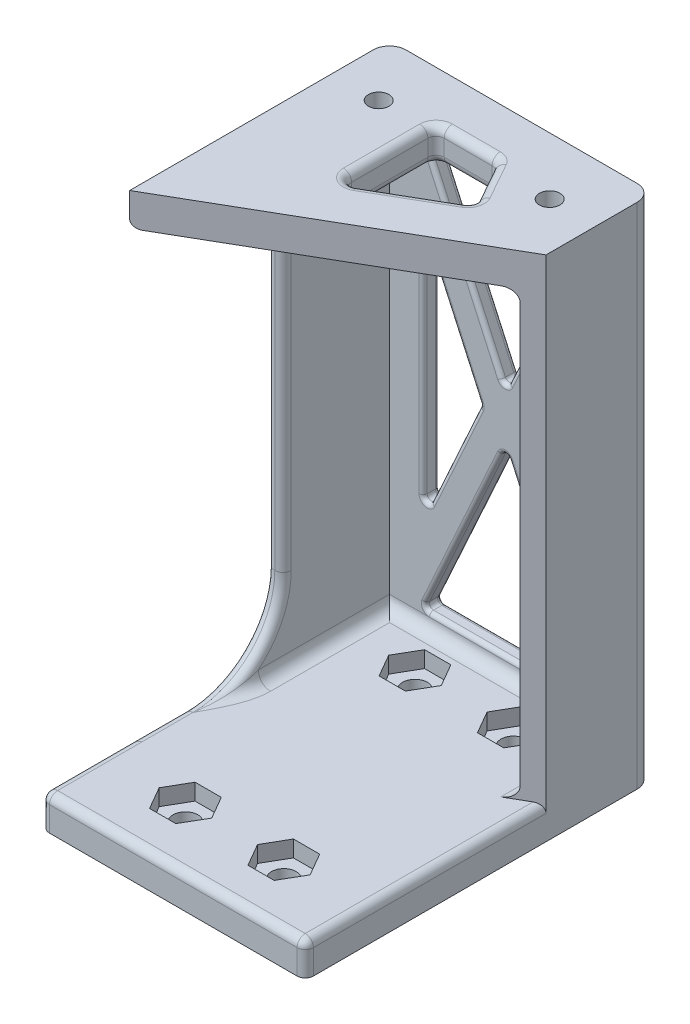
SolidWorks part; units mm, degrees
ref_plane "Front Plane" through (0, 0, 0) normal (0, 0, 1) x (1, 0, 0)
ref_plane "Top Plane" through (0, 0, 0) normal (0, 1, 0) x (1, 0, 0)
ref_plane "Right Plane" through (0, 0, 0) normal (1, 0, 0) x (0, 0, -1)
sketch "Sketch1" plane through (0, 0, 0) normal (0, 1, 0) x (1, 0, 0)
  line L1 (0, 0) -> (32.2, 0)
  line L2 (0, 0) -> (0, 34.25)
  line L3 (0, 34.25) -> (32.2, 34.25)
  line L4 (32.2, 0) -> (32.2, 34.25)
  dimension "D1" = 34.25
  dimension "D2" = 32.2
extrude "Boss-Extrude1" add sketch "Sketch1" along normal blind 4
sketch "Sketch2" plane through (0, 4, 0) normal (0, 1, 0) x (1, 0, 0)
  line L0 (32.2, 34.25) -> (0, 34.25) construction
  line L3 (16.1, 27.25) -> (10.1, 27.25) construction
  line L4 (16.1, 27.25) -> (22.1, 27.25) construction
  line L5 (16.1, 34.25) -> (16.1, 0) construction
  line L6 (0, 0) -> (32.2, 0) construction
  dimension "D1" = 6
  dimension "D2" = 7
ref_plane "Plane1" through (0, 58, 0) normal (0, 1, 0) x (1, 0, 0)
sketch "Sketch5" plane through (0, 58, 0) normal (0, 1, 0) x (1, 0, 0)
  line L1 (0, 34.25) -> (32.2, 34.25)
  line L2 (0, 34.25) -> (0, 0)
  line L3 (0, 0) -> (32.2, 0)
  line L4 (32.2, 34.25) -> (32.2, 0)
  dimension "D1" = 34.25
extrude "Boss-Extrude2" add sketch "Sketch5" along normal blind 4 separate body
sketch "Sketch6" plane through (0, 62, 0) normal (0, 1, 0) x (1, 0, 0)
  line L0 (16.1, 34.25) -> (16.1, 0) construction
  line L1 (32.2, 34.25) -> (0, 34.25) construction
  line L2 (0, 0) -> (32.2, 0) construction
  line L3 (16.1, 27.25) -> (5.67, 27.25) construction
  line L4 (16.1, 27.25) -> (26.53, 27.25) construction
  dimension "D1" = 10.43
  dimension "D2" = 7
sketch "Sketch11" plane through (0, 0, 0) normal (-1, 0, 0) x (0, 0, 1)
  line L0 (-34.25, 4) -> (-34.25, 58)
  line L1 (-34.25, 58) -> (0, 58)
  line L2 (0, 58) -> (0, 4)
  line L3 (0, 4) -> (-34.25, 4)
  line L4 (-34.25, 31) -> (0, 31) construction
extrude "Boss-Extrude3" add sketch "Sketch11" against normal blind 2
sketch "Sketch24" plane through (0, 0, 0) normal (0, -1, 0) x (1, 0, 0)
  line L0 (16.1, -34.25) -> (16.1, 71.9) construction
  line L1 (108.0286, 41.2361) -> (-3.3086, -23.0444)
  line L2 (108.0286, 18.825) -> (108.0286, 124.975) construction
  line L3 (108.0286, 124.975) -> (16.1, 178.05) construction
  line L4 (16.1, 178.05) -> (-75.8286, 124.975) construction
  line L5 (-75.8286, 124.975) -> (-75.8286, 18.825) construction
  line L6 (-75.8286, 18.825) -> (16.1, -34.25) construction
  line L7 (16.1, -34.25) -> (108.0286, 18.825) construction
  line L8 (-3.3086, -23.0444) -> (-39.5686, 39.7597)
  line L9 (108.0286, 41.2361) -> (71.7686, 104.0403)
  line L10 (-39.5686, 39.7597) -> (71.7686, 104.0403)
  circle A0 centre (16.1, 71.9) radius 91.9286 construction
  dimension "D1" = 106.15
  dimension "D2" = 72.52
extrude "Cut-Extrude6" cut sketch "Sketch24" against normal through all
sketch "Sketch26" plane through (32.2, 0, 0) normal (1, 0, 0) x (0, 0, -1)
  line L0 (34.25, 4) -> (34.25, 58)
  line L1 (34.25, 58) -> (2.5435, 58)
  line L2 (2.5435, 58) -> (2.5435, 4)
  line L3 (2.5435, 4) -> (34.25, 4)
extrude "Boss-Extrude5" add sketch "Sketch26" against normal blind 2
sketch "Sketch27" plane through (0, 58, 0) normal (0, 1, 0) x (1, 0, 0)
  line L3 (32.2, 2.5435) -> (30.2, 3.6982)
  line L4 (30.2, 3.6982) -> (30.2, 2.5435)
  line L5 (30.2, 2.5435) -> (32.2, 2.5435)
  line L6 (32.2, 2.5435) -> (30.2, 3.6982)
  line L7 (30.2, 3.6982) -> (30.2, 2.5435)
  line L8 (30.2, 2.5435) -> (32.2, 2.5435)
  dimension "D1" = 0
extrude "Cut-Extrude7" cut sketch "Sketch27" against normal through all
sketch "Sketch28" plane through (32.2, 0, 0) normal (1, 0, 0) x (0, 0, -1)
  line L3 (2.5435, 62) -> (2.5435, 0) construction
  line L7 (19.25, 4) -> (19.25, 58)
  line L8 (19.25, 58) -> (2.5435, 58)
  line L9 (2.5435, 62) -> (34.25, 62) construction
  line L10 (34.25, 0) -> (34.25, 62) construction
  line L11 (2.5435, 0) -> (34.25, 0) construction
  line L12 (19.25, 4) -> (2.5435, 4)
  line L13 (2.5435, 4) -> (2.5435, 58)
  dimension "D1" = 4
  dimension "D4" = 4
  dimension "D6" = 15
extrude "Cut-Extrude8" cut sketch "Sketch28" against normal up to next
sketch "Sketch29" plane through (0, 62, 0) normal (0, 1, 0) x (1, 0, 0)
  line L0 (20.53, 16.2094) -> (9.824, 22.3905)
  line L1 (9.824, 22.3905) -> (13.1097, 28.25)
  line L2 (13.1097, 28.25) -> (20.53, 28.25)
  line L3 (20.53, 28.25) -> (20.53, 16.2094)
  line L4 (32.2, 2.5435) -> (0, 21.1342) construction
  line L5 (32.2, 34.25) -> (0, 34.25) construction
  dimension "D1" = 6
  dimension "D2" = 6
  dimension "D3" = 6
  dimension "D4" = 6
extrude "Cut-Extrude9" cut sketch "Sketch29" against normal up to next
fillet "Fillet2" radius 2 2 edges at (32.2, 31, -34.25) (0, 31, -34.25)
sketch "Sketch31" plane through (2, 0, 0) normal (1, 0, 0) x (0, 0, -1)
  line L0 (34.25, 4) -> (34.25, 58)
  line L1 (34.25, 58) -> (32.25, 58)
  line L2 (19.9795, 58) -> (34.25, 58) construction
  line L3 (32.25, 58) -> (32.25, 4)
  line L4 (34.25, 4) -> (19.9795, 4) construction
  line L5 (32.25, 4) -> (34.25, 4)
  dimension "D1" = 2
extrude "Boss-Extrude6" add sketch "Sketch31" along normal up to next
sketch "Sketch32" plane through (0, 0, -34.25) normal (0, 0, -1) x (-1, 0, 0)
  line L0 (-16.1, 62) -> (-16.1, 0) construction
  line L1 (-30.2, 62) -> (-2, 62) construction
  line L2 (-30.2, 0) -> (-2, 0) construction
  line L3 (-32.2, 31) -> (0, 31) construction
  line L4 (-32.2, 0) -> (-32.2, 62) construction
  line L5 (0, 62) -> (0, 0) construction
  line L6 (-6.0935, 56) -> (-26.1065, 56)
  line L7 (-26.1065, 56) -> (-16.1, 34)
  line L9 (-30.2, 62) -> (-2, 0) construction
  line L10 (-6.0935, 56) -> (-16.1, 34)
  line L11 (-6.0935, 6) -> (-16.1, 28)
  line L12 (-6.0935, 6) -> (-26.1065, 6)
  line L13 (-26.1065, 6) -> (-16.1, 28)
  line L14 (-6.0935, 46.4043) -> (-6.0935, 15.5957)
  line L15 (-6.0935, 46.4043) -> (-13.1, 31)
  line L17 (-6.0935, 15.5957) -> (-13.1, 31)
  line L18 (-26.1065, 46.4043) -> (-26.1065, 15.5957)
  line L19 (-26.1065, 46.4043) -> (-19.1, 31)
  line L20 (-26.1065, 15.5957) -> (-19.1, 31)
  point P14 (-16.1, 31)
  point P29 (-6.0935, 31)
  dimension "D1" = 6
  dimension "D2" = 3
  dimension "D3" = 3
extrude "Cut-Extrude11" cut sketch "Sketch32" against normal up to next
fillet "Fillet3" radius 0.5 36 edges at (9.5968, 38.7021, -32.25) (9.5968, 38.7021, -34.25) (9.5968, 23.2979, -34.25) (9.5968, 23.2979, -32.25) (22.6032, 23.2979, -32.25) (22.6032, 23.2979, -34.25) (22.6032, 38.7021, -34.25) (22.6032, 38.7021, -32.25) (21.1032, 45, -32.25) (21.1032, 45, -34.25) (11.0968, 45, -34.25) (11.0968, 45, -32.25) (11.0968, 17, -32.25) (11.0968, 17, -34.25) (21.1032, 17, -34.25) (21.1032, 17, -32.25) (6.0935, 46.4043, -33.25) (6.0935, 31, -34.25) (6.0935, 15.5957, -33.25) (6.0935, 31, -32.25) (26.1065, 15.5957, -33.25) (26.1065, 31, -34.25) (26.1065, 46.4043, -33.25) (26.1065, 31, -32.25) (26.1065, 56, -33.25) (16.1, 56, -34.25) (6.0935, 56, -33.25) (16.1, 56, -32.25) (6.0935, 6, -33.25) (16.1, 6, -34.25) (26.1065, 6, -33.25) (16.1, 6, -32.25) (19.1, 31, -33.25) (13.1, 31, -33.25) (16.1, 34, -33.25) (16.1, 28, -33.25)
fillet "Fillet4" radius 10 2 edges at (31.2, 58, -19.25) (31.2, 4, -19.25)
fillet "Fillet5" radius 1 8 edges at (32.2, 58, -5.8968) (32.2, 55.0711, -16.3211) (32.2, 31, -19.25) (32.2, 6.9289, -16.3211) (32.2, 4, -5.8968) (30.2, 55.0711, -16.3211) (30.2, 31, -19.25) (30.2, 6.9289, -16.3211)
sketch "Sketch35" plane through (0, 4, 0) normal (0, 1, 0) x (1, 0, 0)
  line L1 (13.3043, 27.25) -> (11.7021, 30.025)
  line L2 (11.7021, 30.025) -> (8.4979, 30.025)
  line L3 (8.4979, 30.025) -> (6.8957, 27.25)
  line L4 (6.8957, 27.25) -> (8.4979, 24.475)
  line L5 (8.4979, 24.475) -> (11.7021, 24.475)
  line L6 (11.7021, 24.475) -> (13.3043, 27.25)
  line L7 (18.8957, 27.25) -> (20.4979, 24.475)
  line L8 (20.4979, 24.475) -> (23.7021, 24.475)
  line L9 (23.7021, 24.475) -> (25.3043, 27.25)
  line L10 (25.3043, 27.25) -> (23.7021, 30.025)
  line L11 (23.7021, 30.025) -> (20.4979, 30.025)
  line L12 (20.4979, 30.025) -> (18.8957, 27.25)
  line L14 (30.2, 34.25) -> (2, 34.25) construction
  circle A0 centre (10.1, 27.25) radius 2.775 construction
  circle A1 centre (22.1, 27.25) radius 2.775 construction
  dimension "D1" = 5.55
extrude "Cut-Extrude14" cut sketch "Sketch35" against normal blind 2
fillet "Fillet6" radius 1.5 8 edges at (30.4594, 58, -11.8326) (30.4594, 4, -11.8326) (2, 58, -26.1148) (16.1, 58, -32.25) (30.2, 58, -23.0413) (30.2, 4, -23.0413) (16.1, 4, -32.25) (2, 4, -26.1148)
sketch "Sketch37" plane through (0, 4, 0) normal (0, 1, 0) x (1, 0, 0)
  circle A0 centre (10.1, 27.25) radius 1.5
  circle A1 centre (22.1, 27.25) radius 1.5
  dimension "D1" = 3
extrude "Cut-Extrude15" cut sketch "Sketch37" against normal blind 10
sketch "Sketch38" plane through (0, 62, 0) normal (0, 1, 0) x (1, 0, 0)
  circle A0 centre (5.67, 27.25) radius 1.25
  circle A1 centre (26.53, 27.25) radius 1.25
  dimension "D1" = 2.5
extrude "Cut-Extrude16" cut sketch "Sketch38" against normal up to next
sketch "Sketch39" plane through (0, 0, 0) normal (0, -1, 0) x (1, 0, 0)
  line L0 (0, -21.1342) -> (0, 8.2337)
  line L1 (0, 8.2337) -> (32.2, 8.2337)
  line L2 (32.2, 8.2337) -> (32.2, -2.5435)
  line L3 (32.2, -2.5435) -> (0, -21.1342)
  line L4 (16.1, -27.25) -> (16.1, 0.75) construction
  line L5 (16.1, 0.75) -> (10.1, 0.75) construction
  line L6 (16.1, 0.75) -> (22.1, 0.75) construction
  line L7 (16.1, -27.25) -> (10.1, -27.25) construction
  circle A0 centre (10.1, 0.75) radius 1.5
  circle A1 centre (22.1, 0.75) radius 1.5
  circle A2 centre (10.1, -27.25) radius 1.5 construction
  dimension "D1" = 28
extrude "Boss-Extrude7" add sketch "Sketch39" against normal blind 4
fillet "Fillet7" radius 1 5 edges at (32.2, 4, 2.8451) (0, 4, -6.4503) (0, 2, 8.2337) (32.2, 2, 8.2337) (16.1, 4, 8.2337)
sketch "Sketch40" plane through (0, 4, 0) normal (0, 1, 0) x (1, 0, 0)
  line L0 (1, -7.2337) -> (31.2, -7.2337) construction
  line L1 (8.4979, -3.525) -> (11.7021, -3.525)
  line L2 (11.7021, -3.525) -> (13.3043, -0.75)
  line L3 (13.3043, -0.75) -> (11.7021, 2.025)
  line L4 (11.7021, 2.025) -> (8.4979, 2.025)
  line L5 (8.4979, 2.025) -> (6.8957, -0.75)
  line L6 (6.8957, -0.75) -> (8.4979, -3.525)
  line L7 (20.4979, -3.525) -> (23.7021, -3.525)
  line L8 (23.7021, -3.525) -> (25.3043, -0.75)
  line L9 (25.3043, -0.75) -> (23.7021, 2.025)
  line L10 (23.7021, 2.025) -> (20.4979, 2.025)
  line L11 (20.4979, 2.025) -> (18.8957, -0.75)
  line L12 (18.8957, -0.75) -> (20.4979, -3.525)
  circle A0 centre (10.1, -0.75) radius 2.775 construction
  circle A1 centre (22.1, -0.75) radius 2.775 construction
  dimension "D1" = 5.55
extrude "Cut-Extrude17" cut sketch "Sketch40" against normal blind 2
fillet "Fillet8" radius 1 12 edges at (16.8199, 58, -28.25) (16.8199, 62, -28.25) (15.177, 62, -19.3) (15.177, 58, -19.3) (9.824, 60, -22.3905) (11.4669, 62, -25.3203) (13.1097, 60, -28.25) (11.4669, 58, -25.3203) (20.53, 60, -28.25) (20.53, 62, -22.2297) (20.53, 60, -16.2094) (20.53, 58, -22.2297)
mirror "Mirror1" about plane through (32.2, 4, 0) normal (-1, 0, 0) of bodies 134
sketch "Sketch41" plane through (0, 0, 0) normal (0, -1, 0) x (-1, 0, 0)
  line L2 (-32.2, 32.25) -> (-32.2, -12.6206)
  line L3 (-32.2, -12.6206) -> (5.8236, -12.6206)
  line L4 (5.8236, 32.25) -> (5.8236, -12.6206)
  line L6 (-32.2, 32.25) -> (-32.2, 36.735)
  line L7 (-32.2, 36.735) -> (5.8236, 36.735)
  line L8 (5.8236, 32.25) -> (5.8236, 36.735)
extrude "Cut-Extrude18" cut sketch "Sketch41" against normal through all
